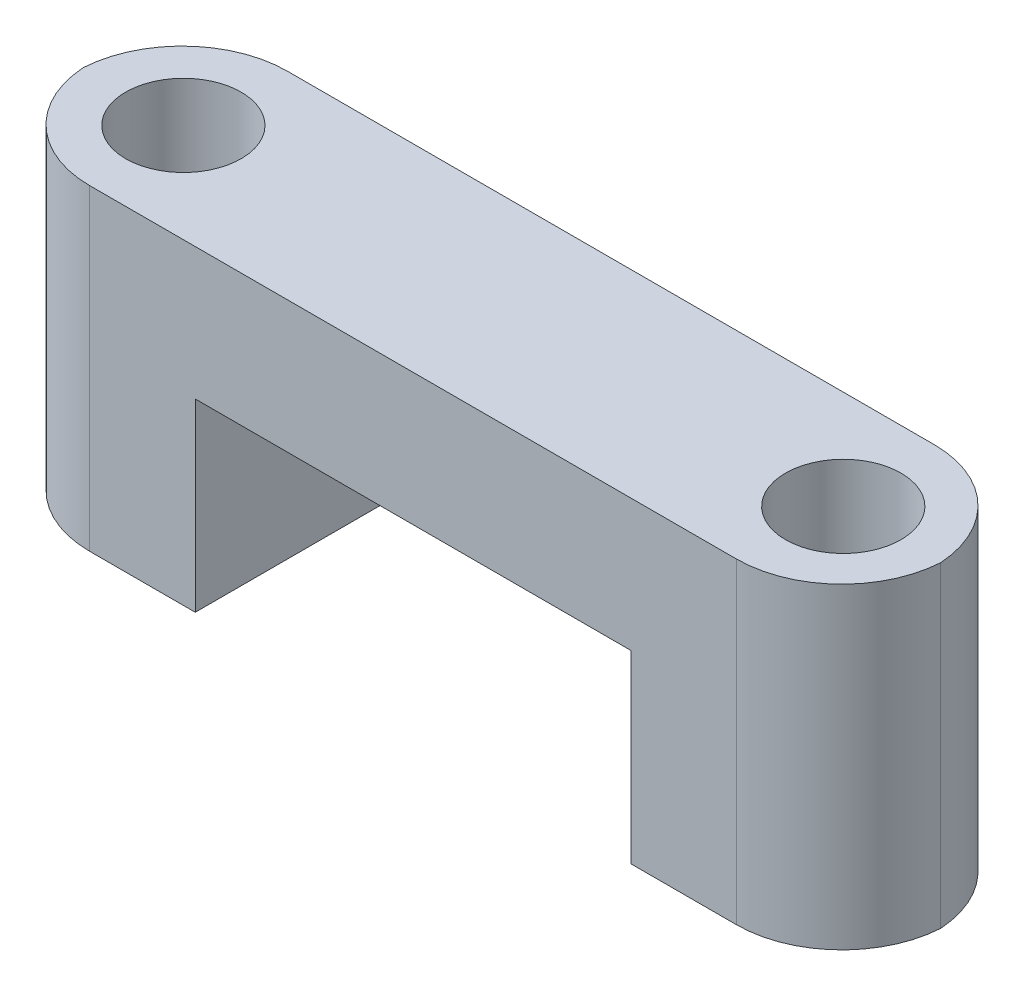
SolidWorks part; units mm, degrees
ref_plane "Front" through (0, 0, 0) normal (0, 0, 1) x (1, 0, 0)
ref_plane "Top" through (0, 0, 0) normal (0, 1, 0) x (1, 0, 0)
ref_plane "Right" through (0, 0, 0) normal (1, 0, 0) x (0, 0, -1)
sketch "Sketch1" plane through (0, 0, 0) normal (0, 1, 0) x (1, 0, 0)
  line L1 (-20.6375, -4.7625) -> (20.6375, -4.7625)
  line L2 (-20.6375, -4.7625) -> (-20.6375, 4.7625)
  line L3 (-20.6375, 4.7625) -> (20.6375, 4.7625)
  line L4 (20.6375, -4.7625) -> (20.6375, 4.7625)
  line L5 (-20.6375, -4.7625) -> (20.6375, 4.7625) construction
  line L6 (-20.6375, 4.7625) -> (20.6375, -4.7625) construction
  point P0 (0, 0)
  dimension "D1" = 41.275
  dimension "D2" = 9.525
extrude "Boss-Extrude1" add sketch "Sketch1" along normal blind 6.35
sketch "Sketch2" plane through (0, 0, 0) normal (0, -1, 0) x (1, 0, 0)
  line L0 (20.6375, -4.7625) -> (-20.6375, -4.7625) construction
  line L1 (-20.6375, 4.7625) -> (-10.4775, 4.7625)
  line L2 (-20.6375, 4.7625) -> (-20.6375, -4.7625)
  line L3 (-20.6375, -4.7625) -> (-10.4775, -4.7625)
  line L4 (-10.4775, 4.7625) -> (-10.4775, -4.7625)
  line L5 (0, 4.7625) -> (0, -4.7625) construction
  line L6 (-20.6375, 4.7625) -> (20.6375, 4.7625) construction
  line L7 (20.6375, -4.7625) -> (10.4775, -4.7625)
  line L8 (10.4775, 4.7625) -> (10.4775, -4.7625)
  line L9 (20.6375, 4.7625) -> (10.4775, 4.7625)
  line L10 (20.6375, 4.7625) -> (20.6375, -4.7625)
  dimension "D1" = 10.16
extrude "Boss-Extrude2" add sketch "Sketch2" along normal blind 8.89
sketch "Sketch3" plane through (0, 6.35, 0) normal (0, 1, 0) x (1, 0, 0)
  line L0 (-20.6375, 4.7625) -> (-20.6375, -4.7625) construction
  point P0 (-15.8115, 0)
  point P1 (15.9385, 0)
  dimension "D1" = 31.75
  dimension "D2" = 4.826
hole_wizard "7/32 (0.21875) Diameter Hole1" positions "Sketch4" profile "Sketch5" hole size "7/32" standard "ANSI Inch" end condition through all
sketch "Sketch4" plane through (0, 6.35, 0) normal (0, 1, 0) x (1, 0, 0)
  point P0 (-15.8115, 0)
  point P3 (15.9385, 0)
sketch "Sketch5" plane through (-15.8115, 6.35, 0) normal (1, 0, 0) x (0, 0, 1)
  line L0 (0, 0) -> (0, 15.24)
  line L1 (0, 15.24) -> (2.7781, 15.24)
  line L2 (2.7781, 15.24) -> (2.7781, 0)
  line L5 (2.7781, 0) -> (0, 0)
  line L11 (0, -6.35) -> (0, 107.95) construction
  dimension "Thru Hole Dia." = 5.5562
  dimension "Thru Hole Depth" = 15.24
fillet "Fillet1" radius 5.08 4 edges at (20.6375, -1.27, -4.7625) (20.6375, -1.27, 4.7625) (-20.6375, -1.27, -4.7625) (-20.6375, -1.27, 4.7625)
